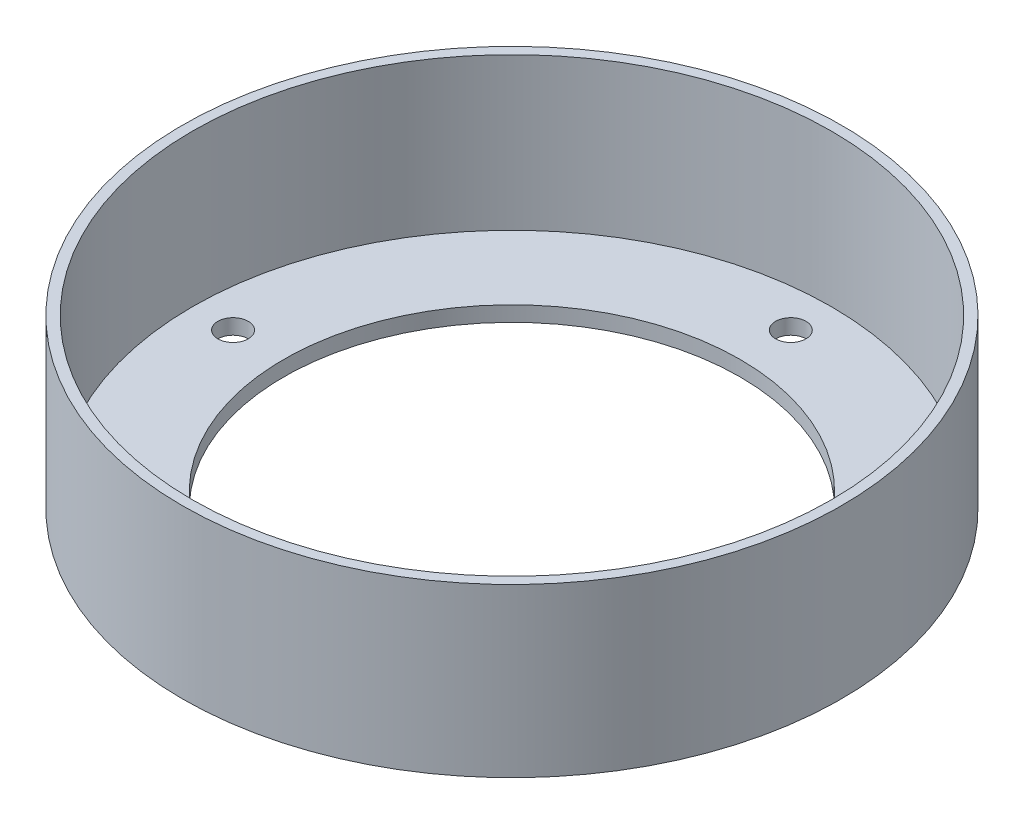
SolidWorks part; units mm, degrees
ref_plane "Front Plane" through (0, 0, 0) normal (0, 0, 1) x (1, 0, 0)
ref_plane "Top Plane" through (0, 0, 0) normal (0, 1, 0) x (1, 0, 0)
ref_plane "Right Plane" through (0, 0, 0) normal (1, 0, 0) x (0, 0, -1)
sketch "Sketch1" plane through (0, 0, 0) normal (0, 1, 0) x (1, 0, 0)
  circle A0 centre (0, 0) radius 65
  dimension "160" = 130
extrude "Boss-Extrude1" add sketch "Sketch1" along normal blind 3
sketch "Sketch2" plane through (0, 3, 0) normal (0, 1, 0) x (1, 0, 0)
  circle A0 centre (0, 0) radius 55 construction
  circle A1 centre (0, 55) radius 3
  dimension "D1" = 110
  dimension "D2" = 6
extrude "Cut-Extrude1" cut sketch "Sketch2" against normal through all
pattern_circular "CirPattern1" count 4 over 360 about axis through (0, 3, 0) along (0, 1, 0) of "Cut-Extrude1"
sketch "Sketch3" plane through (0, 3, 0) normal (0, 1, 0) x (1, 0, 0)
  circle A0 centre (0, 0) radius 65
  circle A1 centre (0, 0) radius 63
  dimension "D1" = 130
  dimension "D2" = 126
extrude "Boss-Extrude2" add sketch "Sketch3" along normal blind 30
sketch "草圖1" plane through (0, 0, 0) normal (0, -1, 0) x (1, 0, 0)
  circle A0 centre (0, 0) radius 45
  dimension "D1" = 90
extrude "除料-伸長1" cut sketch "草圖1" against normal through all
